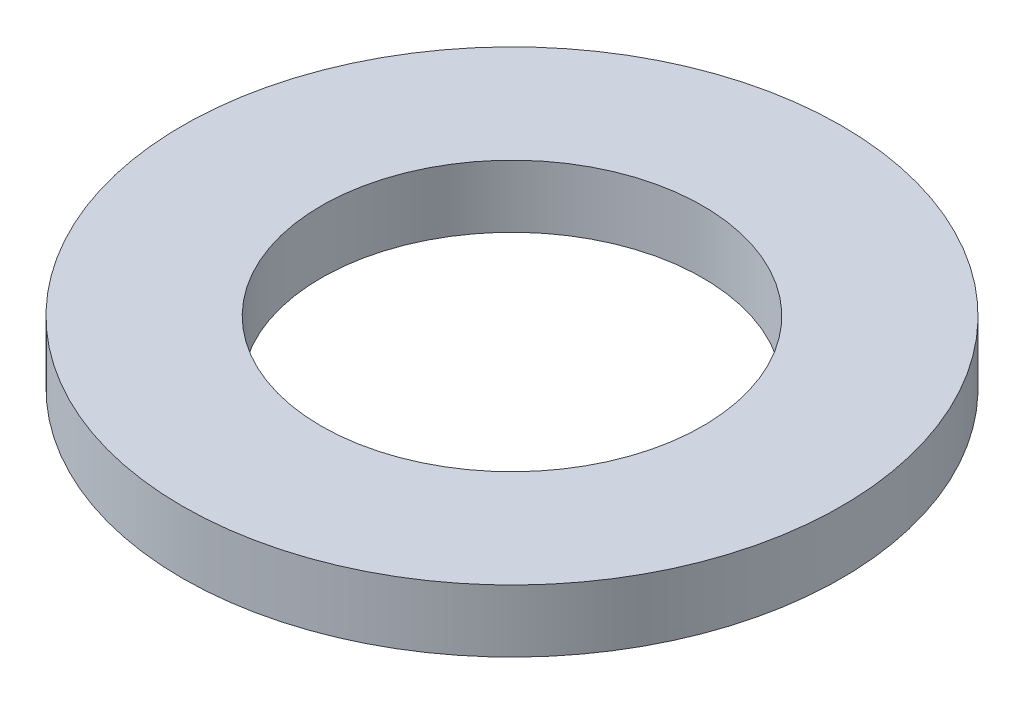
SolidWorks part; units mm, degrees
ref_plane "Front Plane" through (0, 0, 0) normal (0, 0, 1) x (1, 0, 0)
ref_plane "Top Plane" through (0, 0, 0) normal (0, 1, 0) x (1, 0, 0)
ref_plane "Right Plane" through (0, 0, 0) normal (1, 0, 0) x (0, 0, -1)
sketch "Sketch1" plane through (0, 0, 0) normal (0, 1, 0) x (1, 0, 0)
  circle A0 centre (0, 0) radius 47.5
  dimension "FLANGE_OD" = 95
extrude "Boss-Extrude1" add sketch "Sketch1" along normal blind 9
sketch "Sketch2" plane through (0, 0, 0) normal (0, 1, 0) x (1, 0, 0)
  circle A0 centre (0, 0) radius 27.5
  dimension "BORE_D" = 55
extrude "Cut-Extrude1" cut sketch "Sketch2" along normal through all
sketch "Sketch3" plane through (0, 9, 0) normal (0, 1, 0) x (1, 0, 0)
  circle A0 centre (0, 0) radius 17.0486 construction
  circle A1 centre (-17.0486, 0) radius 2.6313
  dimension "BOLT_D" = 5.2626
  dimension "BOLT_PCD" = 34.0971
extrude "Cut-Extrude2" cut sketch "Sketch3" against normal blind 8.2582 rebuild error yes
pattern_circular "CirPattern1" count 8 over 360 rebuild error yes
